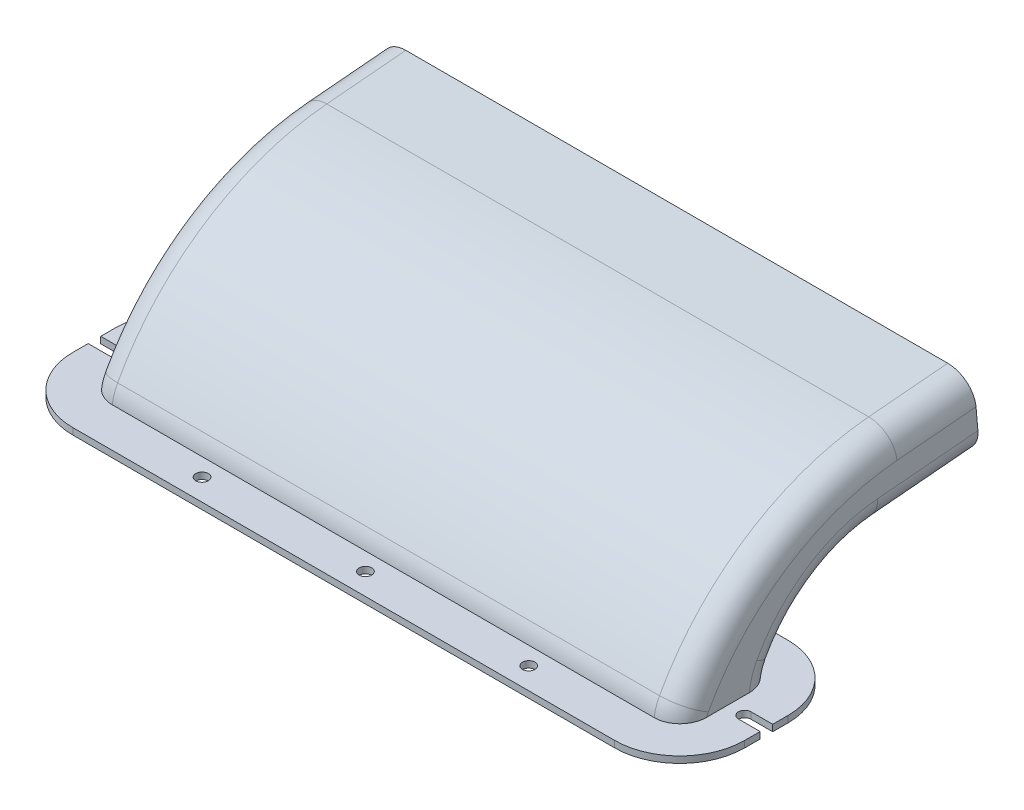
SolidWorks part; units mm, degrees
material "PA Type 6"
ref_plane "Front Plane" through (0, 0, 0) normal (0, 0, 1) x (1, 0, 0)
ref_plane "Top Plane" through (0, 0, 0) normal (0, 1, 0) x (1, 0, 0)
ref_plane "Right Plane" through (0, 0, 0) normal (1, 0, 0) x (0, 0, -1)
sketch "Sketch1" plane through (0, 0, 0) normal (1, 0, 0) x (0, 0, -1)
  line L1 (97.3506, 71.6943) -> (133.8303, 74.8858)
  line L2 (133.8303, 74.8858) -> (136.445, 45)
  line L3 (136.445, 45) -> (90.0615, 40.942)
  line L5 (40, 0) -> (0, 0)
  line L11 (40, 0) -> (40, 15.3277) construction
  arc A0 (2.4381, 9.5698) -> (97.3506, 71.6943) centre (107.8093, -47.8491) cw
  arc A1 (90.0615, 40.942) -> (42.3546, 9.4149) centre (95.2908, -18.8297) ccw
  arc A2 (40, 0) -> (42.3546, 9.4149) centre (60, 0) cw
  arc A3 (0, 0) -> (2.4381, 9.5698) centre (20, 0) cw
  dimension "D5" = 120
  dimension "D6" = 60
  dimension "D9" = 20
  dimension "D10" = 20
  dimension "D1" = 45
  dimension "D2" = 30
  dimension "D4" = 40
  dimension "D7" = 100
  dimension "D8" = 95
extrude "Boss-Extrude1" add sketch "Sketch1" along normal mid plane 270
fillet "Fillet1" radius 10 12 edges at (135, 73.2901, -115.5904) (135, 4.9378, -0.6191) (-135, 73.2901, -115.5904) (-135, 52.5551, -42.0902) (135, 52.5551, -42.0902) (-135, 4.9378, -0.6191) (135, 42.971, -113.2532) (135, 31.2273, -62.2106) (-135, 42.971, -113.2532) (-135, 31.2273, -62.2106) (135, 4.8524, -40.5976) (-135, 4.8524, -40.5976)
shell "Shell1" thickness 2 removed face at (0, 59.9429, -135.1377) removed face at (0, 0, -20) outward yes
sketch "Sketch2" plane through (0, 0, 0) normal (0, -1, 0) x (1, 0, 0)
  line L8 (155, -30) -> (155, -10)
  line L9 (125, 20) -> (-125, 20)
  line L10 (-155, -10) -> (-155, -30)
  line L11 (-125, -60) -> (125, -60)
  line L12 (155, -30) -> (155, -10)
  line L13 (125, 20) -> (-125, 20)
  line L14 (-155, -10) -> (-155, -30)
  line L15 (-125, -60) -> (125, -60)
  line L34 (-136.5, -10) -> (-136.5, -30)
  line L35 (125, 1.5) -> (-125, 1.5)
  line L36 (-125, -41.5) -> (125, -41.5)
  line L37 (136.5, -30) -> (136.5, -10)
  line L38 (-136.5, -10) -> (-136.5, -30)
  line L39 (125, 1.5) -> (-125, 1.5)
  line L40 (-125, -41.5) -> (125, -41.5)
  line L41 (136.5, -30) -> (136.5, -10)
  arc A8 (155, -10) -> (125, 20) centre (125, -10) ccw
  arc A9 (-125, 20) -> (-155, -10) centre (-125, -10) ccw
  arc A10 (-155, -30) -> (-125, -60) centre (-125, -30) ccw
  arc A11 (125, -60) -> (155, -30) centre (125, -30) ccw
  arc A12 (155, -10) -> (125, 20) centre (125, -10) ccw
  arc A13 (-125, 20) -> (-155, -10) centre (-125, -10) ccw
  arc A14 (-155, -30) -> (-125, -60) centre (-125, -30) ccw
  arc A15 (125, -60) -> (155, -30) centre (125, -30) ccw
  arc A34 (-125, 1.5) -> (-136.5, -10) centre (-125, -10) ccw
  arc A35 (-136.5, -30) -> (-125, -41.5) centre (-125, -30) ccw
  arc A36 (125, -41.5) -> (136.5, -30) centre (125, -30) ccw
  arc A37 (136.5, -10) -> (125, 1.5) centre (125, -10) ccw
  arc A38 (-125, 1.5) -> (-136.5, -10) centre (-125, -10) ccw
  arc A39 (-136.5, -30) -> (-125, -41.5) centre (-125, -30) ccw
  arc A40 (125, -41.5) -> (136.5, -30) centre (125, -30) ccw
  arc A41 (136.5, -10) -> (125, 1.5) centre (125, -10) ccw
  dimension "D1" = 18
  dimension "D2" = 0.5
extrude "Boss-Extrude2" add sketch "Sketch2" against normal blind 3
hole_wizard "M5 Clearance Hole1" positions "Sketch3" profile "Sketch4" hole size "M5" standard "ISO"
sketch "Sketch3" plane through (0, 0, 0) normal (0, -1, 0) x (-1, 0, 0)
  point P0 (75.3539, -10)
  point P3 (145, 20)
  point P6 (0, -10)
  point P9 (-75.3539, -10)
  point P12 (-145, 20)
  point P15 (-75.3539, 50)
  point P18 (0, 50)
  point P22 (75.3539, 50)
sketch "Sketch4" plane through (-75.3539, 0, 10) normal (1, 0, 0) x (0, 0, -1)
  line L0 (0, 0) -> (0, 7.7425)
  line L1 (0, 7.7425) -> (2.9, 6)
  line L2 (2.9, 6) -> (2.9, 0)
  line L5 (2.9, 0) -> (0, 0)
  line L10 (0, 7.7425) -> (-2.9, 6) construction
  line L11 (0, -6.35) -> (0, 107.95) construction
  dimension "Hole Dia." = 5.8
  dimension "Hole Depth" = 6
  dimension "Drill Angle" = 118
sketch "Sketch5" plane through (0, 3, 0) normal (0, 1, 0) x (1, 0, 0)
  line L0 (-145, 22.9) -> (-160, 22.9)
  line L1 (-160, 22.9) -> (-160, 17.1)
  line L2 (-160, 17.1) -> (-145, 17.1)
  line L3 (-145, 17.1) -> (-145, 22.9)
  circle A0 centre (-145, 20) radius 2.9 construction
  dimension "D1" = 15
extrude "Cut-Extrude1" cut sketch "Sketch5" against normal through all
mirror "Mirror1" about plane through (0, 0, 0) normal (1, 0, 0) of "Cut-Extrude1"
sketch "Sketch6" plane through (0, 3, 0) normal (0, 1, 0) x (1, 0, 0)
  line L0 (78.2539, 50) -> (78.2539, 66.9127)
  line L1 (78.2539, 66.9127) -> (72.4539, 66.9127)
  line L2 (72.4539, 66.9127) -> (72.4539, 50)
  line L3 (72.4539, 50) -> (78.2539, 50)
  circle A0 centre (75.3539, 50) radius 2.9 construction
extrude "Cut-Extrude2" cut sketch "Sketch6" against normal through all
pattern_linear "LPattern1" count 3 spacing 75.35 along (-1, 0, 0) of "Cut-Extrude2"
